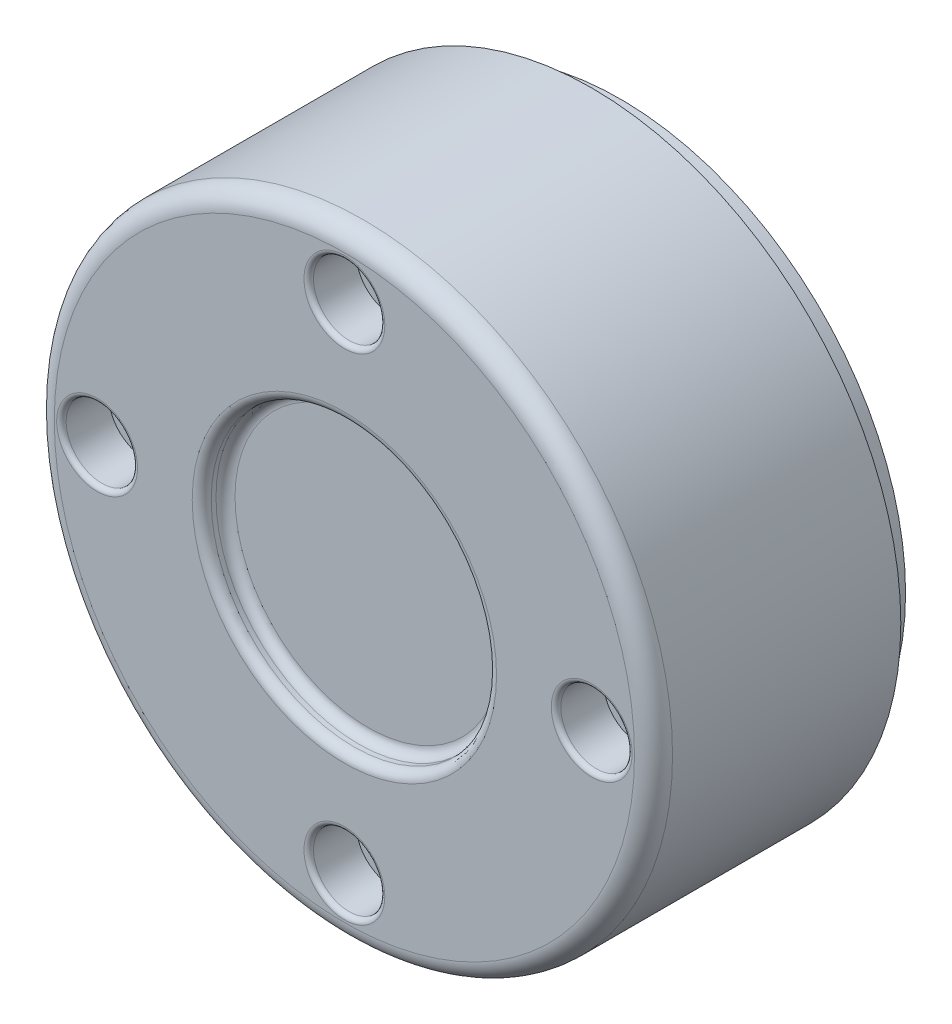
SolidWorks part; units mm, degrees
material "2014-O"
ref_plane "Front Plane" through (0, 0, 0) normal (0, 0, 1) x (1, 0, 0)
ref_plane "Top Plane" through (0, 0, 0) normal (0, 1, 0) x (1, 0, 0)
ref_plane "Right Plane" through (0, 0, 0) normal (1, 0, 0) x (0, 0, -1)
sketch "Sketch2" plane through (0, 0, 0) normal (0, 0, 1) x (1, 0, 0)
  circle A0 centre (0, 0) radius 30
  dimension "D1" = 60
extrude "Boss-Extrude1" add sketch "Sketch2" along normal blind 3
sketch "Sketch3" plane through (0, 0, 3) normal (0, 0, 1) x (1, 0, 0)
  circle A0 centre (0, 0) radius 32.5
  dimension "D1" = 65
extrude "Boss-Extrude2" add sketch "Sketch3" along normal blind 26
sketch "Sketch4" plane through (0, 0, 29) normal (0, 0, 1) x (1, 0, 0)
  line L0 (0, 0) -> (0, 26) construction
  circle A0 centre (0, 0) radius 15
  circle A2 centre (0, 0) radius 32.5 construction
  circle A3 centre (0, 26) radius 3.75
  circle A4 centre (26, 0) radius 3.75
  circle A5 centre (0, -26) radius 3.75
  circle A6 centre (-26, 0) radius 3.75
  point P17 (0, 0)
  dimension "D1" = 30
  dimension "D2" = 26
  dimension "D3" = 7.5
  dimension "D4" = 4
extrude "Cut-Extrude1" cut sketch "Sketch4" against normal blind 2.5 contours A0
extrude "Cut-Extrude2" cut sketch "Sketch4<3>" against normal blind 5 contours A6 | A3 | A4 | A5 region at (0, 26, 29) region at (26, 0, 29) region at (-26, 0, 29)
sketch "Sketch4<3>" plane through (0, 0, 29) normal (0, 0, 1) x (1, 0, 0) same geometry as "Sketch4"
fillet "Fillet1" radius 1 1 edges at (15, 0, 26.5)
fillet "Fillet2" radius 1 1 edges at (15, 0, 29)
fillet "Fillet3" radius 2 1 edges at (32.5, 0, 29)
fillet "Fillet4" radius 0.5 4 edges at (3.75, -26, 29) (29.75, 0, 29) (3.75, 26, 29) (-22.25, 0, 29)
shell "Shell1" thickness 2.5 removed face at (30, 0, 0)
